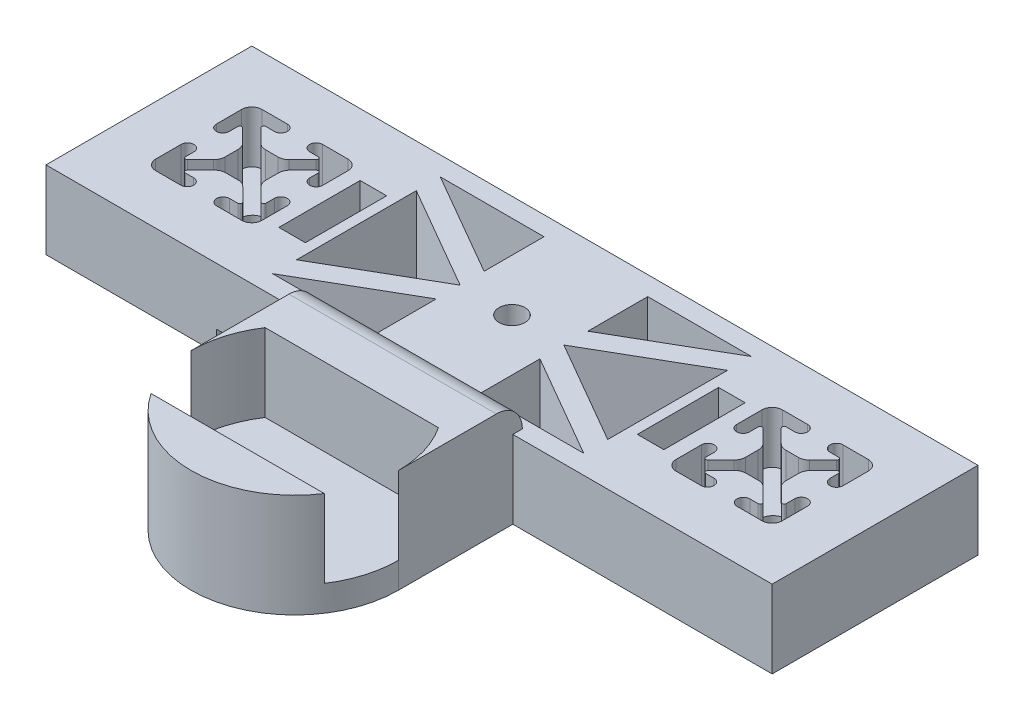
SolidWorks part; units mm, degrees
ref_plane "Front" through (0, 0, 0) normal (0, 0, 1) x (1, 0, 0)
ref_plane "Top" through (0, 0, 0) normal (0, 1, 0) x (1, 0, 0)
ref_plane "Right" through (0, 0, 0) normal (1, 0, 0) x (0, 0, -1)
sketch "Sketch1" plane through (0, 0, 0) normal (0, 1, 0) x (1, 0, 0)
  line L1 (0, 0) -> (177.8, 0)
  line L2 (0, 0) -> (0, 50.4)
  line L3 (0, 50.4) -> (177.8, 50.4)
  line L4 (177.8, 0) -> (177.8, 50.4)
  dimension "D1" = 177.8
  dimension "D2" = 50.4
extrude "Boss-Extrude1" add sketch "Sketch1" along normal blind 6.35
sketch "Sketch2" plane through (0, 6.35, 0) normal (0, 1, 0) x (1, 0, 0)
  line L0 (37.6996, 29.52) -> (37.6996, 35.7372) construction
  line L1 (35.7368, 37.7) -> (29.5196, 37.7) construction
  line L2 (29.5196, 35.56) -> (31.619, 35.56) construction
  line L3 (32.3326, 33.8353) -> (28.9966, 30.504) construction
  line L4 (26.7566, 29.5771) -> (23.643, 29.5771) construction
  line L5 (21.403, 30.504) -> (18.067, 33.8353) construction
  line L6 (18.7806, 35.56) -> (20.88, 35.56) construction
  line L7 (20.88, 37.7) -> (14.6628, 37.7) construction
  line L8 (12.7, 35.7372) -> (12.7, 29.52) construction
  line L9 (14.84, 29.52) -> (14.84, 31.5965) construction
  line L10 (16.5637, 32.3112) -> (19.7659, 29.1135) construction
  line L11 (20.743, 26.7568) -> (20.743, 23.6432) construction
  line L12 (19.7659, 21.2865) -> (16.5637, 18.0888) construction
  line L13 (14.84, 18.8035) -> (14.84, 20.88) construction
  line L14 (12.7, 20.88) -> (12.7, 14.6628) construction
  line L15 (14.6628, 12.7) -> (20.8121, 12.7) construction
  line L16 (20.8121, 14.84) -> (18.7806, 14.84) construction
  line L17 (18.067, 16.5647) -> (21.403, 19.896) construction
  line L18 (23.643, 20.8229) -> (26.7566, 20.8229) construction
  line L19 (28.9966, 19.896) -> (32.3326, 16.5647) construction
  line L20 (31.619, 14.84) -> (29.5875, 14.84) construction
  line L21 (29.5875, 12.7) -> (35.7368, 12.7) construction
  line L22 (37.6996, 14.6628) -> (37.6996, 20.88) construction
  line L23 (35.5596, 20.88) -> (35.5596, 18.8035) construction
  line L24 (33.8359, 18.0888) -> (30.6337, 21.2865) construction
  line L25 (29.6566, 23.6432) -> (29.6566, 26.7568) construction
  line L26 (30.6337, 29.1135) -> (33.8359, 32.3112) construction
  line L27 (35.5596, 31.5965) -> (35.5596, 29.52) construction
  line L28 (0, 50.4) -> (0, 0) construction
  line L29 (177.8, 50.4) -> (0, 50.4) construction
  line L30 (0, 0) -> (177.8, 0) construction
  line L31 (88.9, 50.4) -> (88.9, 0) construction
  line L32 (142.2404, 31.5965) -> (142.2404, 29.52) construction
  line L33 (147.1663, 29.1135) -> (143.9641, 32.3112) construction
  line L34 (148.1434, 23.6432) -> (148.1434, 26.7568) construction
  line L35 (143.9641, 18.0888) -> (147.1663, 21.2865) construction
  line L36 (142.2404, 20.88) -> (142.2404, 18.8035) construction
  line L37 (140.1004, 14.6628) -> (140.1004, 20.88) construction
  line L38 (148.2125, 12.7) -> (142.0632, 12.7) construction
  line L39 (146.181, 14.84) -> (148.2125, 14.84) construction
  line L40 (148.8034, 19.896) -> (145.4674, 16.5647) construction
  line L41 (154.157, 20.8229) -> (151.0434, 20.8229) construction
  line L42 (159.733, 16.5647) -> (156.397, 19.896) construction
  line L43 (156.9879, 14.84) -> (159.0194, 14.84) construction
  line L44 (163.1372, 12.7) -> (156.9879, 12.7) construction
  line L45 (165.1, 20.88) -> (165.1, 14.6628) construction
  line L46 (162.96, 18.8035) -> (162.96, 20.88) construction
  line L47 (158.0341, 21.2865) -> (161.2363, 18.0888) construction
  line L48 (157.057, 26.7568) -> (157.057, 23.6432) construction
  line L49 (161.2363, 32.3112) -> (158.0341, 29.1135) construction
  line L50 (162.96, 29.52) -> (162.96, 31.5965) construction
  line L51 (165.1, 35.7372) -> (165.1, 29.52) construction
  line L52 (156.92, 37.7) -> (163.1372, 37.7) construction
  line L53 (159.0194, 35.56) -> (156.92, 35.56) construction
  line L54 (156.397, 30.504) -> (159.733, 33.8353) construction
  line L55 (151.0434, 29.5771) -> (154.157, 29.5771) construction
  line L56 (145.4674, 33.8353) -> (148.8034, 30.504) construction
  line L57 (148.2804, 35.56) -> (146.181, 35.56) construction
  line L58 (142.0632, 37.7) -> (148.2804, 37.7) construction
  line L59 (140.1004, 29.52) -> (140.1004, 35.7372) construction
  line L60 (38.2076, 29.52) -> (38.2076, 35.7372)
  line L62 (0, 50.4) -> (0, 0)
  line L63 (0, 0) -> (177.8, 0)
  line L64 (177.8, 50.4) -> (177.8, 0)
  line L65 (35.7368, 38.208) -> (29.5196, 38.208)
  line L66 (29.5196, 35.052) -> (31.619, 35.052)
  line L67 (31.9737, 34.1948) -> (28.6376, 30.8635)
  line L68 (26.7566, 30.0851) -> (23.643, 30.0851)
  line L69 (21.762, 30.8635) -> (18.4259, 34.1948)
  line L70 (18.7806, 35.052) -> (20.88, 35.052)
  line L71 (20.88, 38.208) -> (14.6628, 38.208)
  line L72 (12.192, 35.7372) -> (12.192, 29.52)
  line L73 (15.348, 29.52) -> (15.348, 31.5965)
  line L74 (16.2047, 31.9517) -> (19.4069, 28.7541)
  line L75 (20.235, 26.7568) -> (20.235, 23.6432)
  line L76 (19.4069, 21.6459) -> (16.2047, 18.4483)
  line L77 (15.348, 18.8035) -> (15.348, 20.88)
  line L78 (12.192, 20.88) -> (12.192, 14.6628)
  line L79 (14.6628, 12.192) -> (20.8121, 12.192)
  line L80 (20.8121, 15.348) -> (18.7806, 15.348)
  line L81 (18.4259, 16.2052) -> (21.762, 19.5365)
  line L82 (23.643, 20.3149) -> (26.7566, 20.3149)
  line L83 (28.6376, 19.5365) -> (31.9737, 16.2052)
  line L84 (31.619, 15.348) -> (29.5875, 15.348)
  line L85 (29.5875, 12.192) -> (35.7368, 12.192)
  line L86 (38.2076, 14.6628) -> (38.2076, 20.88)
  line L87 (35.0516, 20.88) -> (35.0516, 18.8035)
  line L88 (34.1949, 18.4483) -> (30.9927, 21.6459)
  line L89 (30.1646, 23.6432) -> (30.1646, 26.7568)
  line L90 (30.9927, 28.7541) -> (34.1949, 31.9517)
  line L91 (35.0516, 31.5965) -> (35.0516, 29.52)
  line L92 (142.7484, 31.5965) -> (142.7484, 29.52)
  line L93 (139.5924, 29.52) -> (139.5924, 35.7372)
  line L94 (142.0632, 38.208) -> (148.2804, 38.208)
  line L95 (148.2804, 35.052) -> (146.181, 35.052)
  line L96 (145.8263, 34.1948) -> (149.1624, 30.8635)
  line L97 (151.0434, 30.0851) -> (154.157, 30.0851)
  line L98 (156.038, 30.8635) -> (159.3741, 34.1948)
  line L99 (159.0194, 35.052) -> (156.92, 35.052)
  line L100 (156.92, 38.208) -> (163.1372, 38.208)
  line L101 (165.608, 35.7372) -> (165.608, 29.52)
  line L102 (162.452, 29.52) -> (162.452, 31.5965)
  line L103 (161.5953, 31.9517) -> (158.3931, 28.7541)
  line L104 (157.565, 26.7568) -> (157.565, 23.6432)
  line L105 (158.3931, 21.6459) -> (161.5953, 18.4483)
  line L106 (162.452, 18.8035) -> (162.452, 20.88)
  line L107 (165.608, 20.88) -> (165.608, 14.6628)
  line L108 (163.1372, 12.192) -> (156.9879, 12.192)
  line L109 (156.9879, 15.348) -> (159.0194, 15.348)
  line L110 (159.3741, 16.2052) -> (156.038, 19.5365)
  line L111 (154.157, 20.3149) -> (151.0434, 20.3149)
  line L112 (149.1624, 19.5365) -> (145.8263, 16.2052)
  line L113 (146.181, 15.348) -> (148.2125, 15.348)
  line L114 (148.2125, 12.192) -> (142.0632, 12.192)
  line L115 (139.5924, 14.6628) -> (139.5924, 20.88)
  line L116 (142.7484, 20.88) -> (142.7484, 18.8035)
  line L117 (143.6051, 18.4483) -> (146.8073, 21.6459)
  line L118 (147.6354, 23.6432) -> (147.6354, 26.7568)
  line L119 (146.8073, 28.7541) -> (143.6051, 31.9517)
  line L120 (177.8, 50.4) -> (0, 50.4)
  arc A1 (37.6996, 35.7372) -> (35.7368, 37.7) centre (35.7368, 35.7372) ccw construction
  arc A2 (29.5196, 37.7) -> (29.5196, 35.56) centre (29.5196, 36.63) ccw construction
  arc A3 (31.619, 35.56) -> (32.3326, 33.8353) centre (31.619, 34.55) cw construction
  arc A4 (28.9966, 30.504) -> (26.7566, 29.5771) centre (26.7566, 32.7471) cw construction
  arc A5 (23.643, 29.5771) -> (21.403, 30.504) centre (23.643, 32.7471) cw construction
  arc A6 (18.067, 33.8353) -> (18.7806, 35.56) centre (18.7806, 34.55) cw construction
  arc A7 (20.88, 35.56) -> (20.88, 37.7) centre (20.88, 36.63) ccw construction
  arc A8 (14.6628, 37.7) -> (12.7, 35.7372) centre (14.6628, 35.7372) ccw construction
  arc A9 (12.7, 29.52) -> (14.84, 29.52) centre (13.77, 29.52) ccw construction
  arc A10 (14.84, 31.5965) -> (16.5637, 32.3112) centre (15.85, 31.5965) cw construction
  arc A11 (19.7659, 29.1135) -> (20.743, 26.7568) centre (17.4126, 26.7568) cw construction
  arc A12 (20.743, 23.6432) -> (19.7659, 21.2865) centre (17.4126, 23.6432) cw construction
  arc A13 (16.5637, 18.0888) -> (14.84, 18.8035) centre (15.85, 18.8035) cw construction
  arc A14 (14.84, 20.88) -> (12.7, 20.88) centre (13.77, 20.88) ccw construction
  arc A15 (12.7, 14.6628) -> (14.6628, 12.7) centre (14.6628, 14.6628) ccw construction
  arc A16 (20.8121, 12.7) -> (20.8121, 14.84) centre (20.8121, 13.77) ccw construction
  arc A17 (18.7806, 14.84) -> (18.067, 16.5647) centre (18.7806, 15.85) cw construction
  arc A18 (21.403, 19.896) -> (23.643, 20.8229) centre (23.643, 17.6529) cw construction
  arc A19 (26.7566, 20.8229) -> (28.9966, 19.896) centre (26.7566, 17.6529) cw construction
  arc A20 (32.3326, 16.5647) -> (31.619, 14.84) centre (31.619, 15.85) cw construction
  arc A21 (29.5875, 14.84) -> (29.5875, 12.7) centre (29.5875, 13.77) ccw construction
  arc A22 (35.7368, 12.7) -> (37.6996, 14.6628) centre (35.7368, 14.6628) ccw construction
  arc A23 (37.6996, 20.88) -> (35.5596, 20.88) centre (36.6296, 20.88) ccw construction
  arc A24 (35.5596, 18.8035) -> (33.8359, 18.0888) centre (34.5496, 18.8035) cw construction
  arc A25 (30.6337, 21.2865) -> (29.6566, 23.6432) centre (32.987, 23.6432) cw construction
  arc A26 (29.6566, 26.7568) -> (30.6337, 29.1135) centre (32.987, 26.7568) cw construction
  arc A27 (33.8359, 32.3112) -> (35.5596, 31.5965) centre (34.5496, 31.5965) cw construction
  arc A28 (35.5596, 29.52) -> (37.6996, 29.52) centre (36.6296, 29.52) ccw construction
  arc A29 (142.2404, 29.52) -> (140.1004, 29.52) centre (141.1704, 29.52) cw construction
  arc A30 (143.9641, 32.3112) -> (142.2404, 31.5965) centre (143.2504, 31.5965) ccw construction
  arc A31 (148.1434, 26.7568) -> (147.1663, 29.1135) centre (144.813, 26.7568) ccw construction
  arc A32 (147.1663, 21.2865) -> (148.1434, 23.6432) centre (144.813, 23.6432) ccw construction
  arc A33 (142.2404, 18.8035) -> (143.9641, 18.0888) centre (143.2504, 18.8035) ccw construction
  arc A34 (140.1004, 20.88) -> (142.2404, 20.88) centre (141.1704, 20.88) cw construction
  arc A35 (142.0632, 12.7) -> (140.1004, 14.6628) centre (142.0632, 14.6628) cw construction
  arc A36 (148.2125, 14.84) -> (148.2125, 12.7) centre (148.2125, 13.77) cw construction
  arc A37 (145.4674, 16.5647) -> (146.181, 14.84) centre (146.181, 15.85) ccw construction
  arc A38 (151.0434, 20.8229) -> (148.8034, 19.896) centre (151.0434, 17.6529) ccw construction
  arc A39 (156.397, 19.896) -> (154.157, 20.8229) centre (154.157, 17.6529) ccw construction
  arc A40 (159.0194, 14.84) -> (159.733, 16.5647) centre (159.0194, 15.85) ccw construction
  arc A41 (156.9879, 12.7) -> (156.9879, 14.84) centre (156.9879, 13.77) cw construction
  arc A42 (165.1, 14.6628) -> (163.1372, 12.7) centre (163.1372, 14.6628) cw construction
  arc A43 (162.96, 20.88) -> (165.1, 20.88) centre (164.03, 20.88) cw construction
  arc A44 (161.2363, 18.0888) -> (162.96, 18.8035) centre (161.95, 18.8035) ccw construction
  arc A45 (157.057, 23.6432) -> (158.0341, 21.2865) centre (160.3874, 23.6432) ccw construction
  arc A46 (158.0341, 29.1135) -> (157.057, 26.7568) centre (160.3874, 26.7568) ccw construction
  arc A47 (162.96, 31.5965) -> (161.2363, 32.3112) centre (161.95, 31.5965) ccw construction
  arc A48 (165.1, 29.52) -> (162.96, 29.52) centre (164.03, 29.52) cw construction
  arc A49 (163.1372, 37.7) -> (165.1, 35.7372) centre (163.1372, 35.7372) cw construction
  arc A50 (156.92, 35.56) -> (156.92, 37.7) centre (156.92, 36.63) cw construction
  arc A51 (159.733, 33.8353) -> (159.0194, 35.56) centre (159.0194, 34.55) ccw construction
  arc A52 (154.157, 29.5771) -> (156.397, 30.504) centre (154.157, 32.7471) ccw construction
  arc A53 (148.8034, 30.504) -> (151.0434, 29.5771) centre (151.0434, 32.7471) ccw construction
  arc A54 (146.181, 35.56) -> (145.4674, 33.8353) centre (146.181, 34.55) ccw construction
  arc A55 (148.2804, 37.7) -> (148.2804, 35.56) centre (148.2804, 36.63) cw construction
  arc A56 (140.1004, 35.7372) -> (142.0632, 37.7) centre (142.0632, 35.7372) cw construction
  arc A58 (38.2076, 35.7372) -> (35.7368, 38.208) centre (35.7368, 35.7372) ccw
  arc A59 (29.5196, 38.208) -> (29.5196, 35.052) centre (29.5196, 36.63) ccw
  arc A60 (31.619, 35.052) -> (31.9737, 34.1948) centre (31.619, 34.55) cw
  arc A61 (28.6376, 30.8635) -> (26.7566, 30.0851) centre (26.7566, 32.7471) cw
  arc A62 (23.643, 30.0851) -> (21.762, 30.8635) centre (23.643, 32.7471) cw
  arc A63 (18.4259, 34.1948) -> (18.7806, 35.052) centre (18.7806, 34.55) cw
  arc A64 (20.88, 35.052) -> (20.88, 38.208) centre (20.88, 36.63) ccw
  arc A65 (14.6628, 38.208) -> (12.192, 35.7372) centre (14.6628, 35.7372) ccw
  arc A66 (12.192, 29.52) -> (15.348, 29.52) centre (13.77, 29.52) ccw
  arc A67 (15.348, 31.5965) -> (16.2047, 31.9517) centre (15.85, 31.5965) cw
  arc A68 (19.4069, 28.7541) -> (20.235, 26.7568) centre (17.4126, 26.7568) cw
  arc A69 (20.235, 23.6432) -> (19.4069, 21.6459) centre (17.4126, 23.6432) cw
  arc A70 (16.2047, 18.4483) -> (15.348, 18.8035) centre (15.85, 18.8035) cw
  arc A71 (15.348, 20.88) -> (12.192, 20.88) centre (13.77, 20.88) ccw
  arc A72 (12.192, 14.6628) -> (14.6628, 12.192) centre (14.6628, 14.6628) ccw
  arc A73 (20.8121, 12.192) -> (20.8121, 15.348) centre (20.8121, 13.77) ccw
  arc A74 (18.7806, 15.348) -> (18.4259, 16.2052) centre (18.7806, 15.85) cw
  arc A75 (21.762, 19.5365) -> (23.643, 20.3149) centre (23.643, 17.6529) cw
  arc A76 (26.7566, 20.3149) -> (28.6376, 19.5365) centre (26.7566, 17.6529) cw
  arc A77 (31.9737, 16.2052) -> (31.619, 15.348) centre (31.619, 15.85) cw
  arc A78 (29.5875, 15.348) -> (29.5875, 12.192) centre (29.5875, 13.77) ccw
  arc A79 (35.7368, 12.192) -> (38.2076, 14.6628) centre (35.7368, 14.6628) ccw
  arc A80 (38.2076, 20.88) -> (35.0516, 20.88) centre (36.6296, 20.88) ccw
  arc A81 (35.0516, 18.8035) -> (34.1949, 18.4483) centre (34.5496, 18.8035) cw
  arc A82 (30.9927, 21.6459) -> (30.1646, 23.6432) centre (32.987, 23.6432) cw
  arc A83 (30.1646, 26.7568) -> (30.9927, 28.7541) centre (32.987, 26.7568) cw
  arc A84 (34.1949, 31.9517) -> (35.0516, 31.5965) centre (34.5496, 31.5965) cw
  arc A85 (35.0516, 29.52) -> (38.2076, 29.52) centre (36.6296, 29.52) ccw
  arc A86 (142.7484, 29.52) -> (139.5924, 29.52) centre (141.1704, 29.52) cw
  arc A87 (139.5924, 35.7372) -> (142.0632, 38.208) centre (142.0632, 35.7372) cw
  arc A88 (148.2804, 38.208) -> (148.2804, 35.052) centre (148.2804, 36.63) cw
  arc A89 (146.181, 35.052) -> (145.8263, 34.1948) centre (146.181, 34.55) ccw
  arc A90 (149.1624, 30.8635) -> (151.0434, 30.0851) centre (151.0434, 32.7471) ccw
  arc A91 (154.157, 30.0851) -> (156.038, 30.8635) centre (154.157, 32.7471) ccw
  arc A92 (159.3741, 34.1948) -> (159.0194, 35.052) centre (159.0194, 34.55) ccw
  arc A93 (156.92, 35.052) -> (156.92, 38.208) centre (156.92, 36.63) cw
  arc A94 (163.1372, 38.208) -> (165.608, 35.7372) centre (163.1372, 35.7372) cw
  arc A95 (165.608, 29.52) -> (162.452, 29.52) centre (164.03, 29.52) cw
  arc A96 (162.452, 31.5965) -> (161.5953, 31.9517) centre (161.95, 31.5965) ccw
  arc A97 (158.3931, 28.7541) -> (157.565, 26.7568) centre (160.3874, 26.7568) ccw
  arc A98 (157.565, 23.6432) -> (158.3931, 21.6459) centre (160.3874, 23.6432) ccw
  arc A99 (161.5953, 18.4483) -> (162.452, 18.8035) centre (161.95, 18.8035) ccw
  arc A100 (162.452, 20.88) -> (165.608, 20.88) centre (164.03, 20.88) cw
  arc A101 (165.608, 14.6628) -> (163.1372, 12.192) centre (163.1372, 14.6628) cw
  arc A102 (156.9879, 12.192) -> (156.9879, 15.348) centre (156.9879, 13.77) cw
  arc A103 (159.0194, 15.348) -> (159.3741, 16.2052) centre (159.0194, 15.85) ccw
  arc A104 (156.038, 19.5365) -> (154.157, 20.3149) centre (154.157, 17.6529) ccw
  arc A105 (151.0434, 20.3149) -> (149.1624, 19.5365) centre (151.0434, 17.6529) ccw
  arc A106 (145.8263, 16.2052) -> (146.181, 15.348) centre (146.181, 15.85) ccw
  arc A107 (148.2125, 15.348) -> (148.2125, 12.192) centre (148.2125, 13.77) cw
  arc A108 (142.0632, 12.192) -> (139.5924, 14.6628) centre (142.0632, 14.6628) cw
  arc A109 (139.5924, 20.88) -> (142.7484, 20.88) centre (141.1704, 20.88) cw
  arc A110 (142.7484, 18.8035) -> (143.6051, 18.4483) centre (143.2504, 18.8035) ccw
  arc A111 (146.8073, 21.6459) -> (147.6354, 23.6432) centre (144.813, 23.6432) ccw
  arc A112 (147.6354, 26.7568) -> (146.8073, 28.7541) centre (144.813, 26.7568) ccw
  arc A113 (143.6051, 31.9517) -> (142.7484, 31.5965) centre (143.2504, 31.5965) ccw
  dimension "D2" = 1.07
  dimension "D3" = 3.17
  dimension "D4" = 3.3305
  dimension "D8" = 1.9628
  dimension "D9" = 1.01
  dimension "D5" = 12.7
  dimension "D6" = 12.7
  dimension "D7" = 12.7
  dimension "D10" = 16.5637
  dimension "D12" = 0.508
  dimension "D13" = 0.508
extrude "Boss-Extrude2" add sketch "Sketch2" along normal blind 12.7
sketch "Sketch3" plane through (0, 19.05, 0) normal (0, 1, 0) x (1, 0, 0)
  line L0 (177.8, 50.4) -> (0, 50.4) construction
  line L1 (0, 50.4) -> (0, 0) construction
  circle A0 centre (88.9, 25.2) radius 3.175
  point P4 (88.9, 50.4)
  point P7 (0, 25.2)
  dimension "D1" = 6.35
extrude "Cut-Extrude1" cut sketch "Sketch3" against normal blind 10.16
sketch "Sketch4" plane through (0, 19.05, 0) normal (0, 1, 0) x (1, 0, 0)
  line L0 (50.8, 45.7306) -> (76.2, 45.7306)
  line L1 (76.2, 45.7306) -> (76.2, 31.0659)
  line L2 (76.2, 31.0659) -> (50.8, 45.7306)
  line L3 (76.2, 19.3341) -> (76.2, 4.6694)
  line L4 (76.2, 4.6694) -> (50.8, 4.6694)
  line L5 (50.8, 4.6694) -> (76.2, 19.3341)
  line L6 (50.8, 39.8647) -> (50.8, 10.5353)
  line L7 (50.8, 10.5353) -> (76.2, 25.2)
  line L8 (76.2, 25.2) -> (50.8, 39.8647)
  line L9 (0, 50.4) -> (0, 0) construction
  line L10 (88.9, 50.4) -> (88.9, 0) construction
  line L11 (177.8, 50.4) -> (0, 50.4) construction
  line L12 (0, 0) -> (177.8, 0) construction
  line L13 (101.6, 25.2) -> (127, 39.8647)
  line L14 (127, 10.5353) -> (101.6, 25.2)
  line L15 (127, 39.8647) -> (127, 10.5353)
  line L16 (127, 4.6694) -> (101.6, 19.3341)
  line L17 (101.6, 4.6694) -> (127, 4.6694)
  line L18 (101.6, 19.3341) -> (101.6, 4.6694)
  line L19 (101.6, 31.0659) -> (127, 45.7306)
  line L20 (101.6, 45.7306) -> (101.6, 31.0659)
  line L21 (127, 45.7306) -> (101.6, 45.7306)
  point P18 (88.9, 25.2)
  dimension "D1" = 25.4
  dimension "D2" = 25.4
  dimension "D3" = 50.8
  dimension "D4" = 5.08
  dimension "D5" = 5.08
  dimension "D7" = 60
extrude "Cut-Extrude2" cut sketch "Sketch4" against normal through all
sketch "Sketch5" plane through (0, 19.05, 0) normal (0, 1, 0) x (1, 0, 0)
  line L0 (0, 50.4) -> (0, 0) construction
  line L1 (41.7636, 35.15) -> (48.2636, 35.15)
  line L2 (41.7636, 35.15) -> (41.7636, 15.25)
  line L3 (41.7636, 15.25) -> (48.2636, 15.25)
  line L4 (48.2636, 35.15) -> (48.2636, 15.25)
  line L5 (38.2076, 29.52) -> (38.2076, 35.7372) construction
  point P6 (0, 25.2)
  point P7 (48.2636, 25.2)
  dimension "D1" = 6.5
  dimension "D2" = 19.9
  dimension "D3" = 3.556
extrude "Cut-Extrude3" cut sketch "Sketch5" against normal blind 10.2
sketch "Sketch6" plane through (0, 8.85, 0) normal (0, 1, 0) x (1, 0, 0)
  line L0 (48.2636, 15.25) -> (48.2636, 35.15) construction
  line L1 (41.7636, 35.15) -> (48.2636, 35.15)
  line L2 (41.7636, 35.15) -> (41.7636, 30.578)
  line L3 (41.7636, 30.578) -> (48.2636, 30.578)
  line L4 (48.2636, 35.15) -> (48.2636, 30.578)
  line L5 (41.7636, 35.15) -> (41.7636, 15.25) construction
  line L6 (48.2636, 15.25) -> (48.2636, 35.15) construction
  line L7 (41.7636, 27.486) -> (48.2636, 27.486)
  line L8 (41.7636, 27.486) -> (41.7636, 22.914)
  line L9 (41.7636, 22.914) -> (48.2636, 22.914)
  line L10 (48.2636, 27.486) -> (48.2636, 22.914)
  line L12 (41.7636, 15.25) -> (48.2636, 15.25)
  line L13 (41.7636, 15.25) -> (41.7636, 19.822)
  line L14 (41.7636, 19.822) -> (48.2636, 19.822)
  line L15 (48.2636, 15.25) -> (48.2636, 19.822)
  line L16 (41.7636, 25.2) -> (0, 25.2) construction
  line L17 (0, 50.4) -> (0, 0) construction
  dimension "D1" = 4.572
extrude "Cut-Extrude4" cut sketch "Sketch6" against normal through all
ref_plane "Plane1" through (88.9, 0, 0) normal (-1, 0, 0) x (0, 0, 1)
mirror "Mirror1" about plane through (88.9, 0, 0) normal (-1, 0, 0) of "Cut-Extrude4", "Cut-Extrude3"
sketch "Sketch7" plane through (0, 6.35, 0) normal (0, 1, 0) x (1, 0, 0)
  line L0 (26.7566, 30.0851) -> (23.643, 30.0851) construction
  line L1 (30.1646, 23.6432) -> (30.1646, 26.7568) construction
  circle A0 centre (25.3386, 25.2591) radius 2.921
  dimension "D1" = 5.842
  dimension "D2" = 4.826
  dimension "D3" = 4.826
extrude "Cut-Extrude5" cut sketch "Sketch7" against normal through all both and the other way through all
sketch "Sketch8" plane through (0, 6.35, 0) normal (0, 1, 0) x (1, 0, 0)
  line L0 (154.157, 30.0851) -> (151.0434, 30.0851) construction
  line L1 (157.565, 23.6432) -> (157.565, 26.7568) construction
  circle A0 centre (152.739, 25.2591) radius 2.921
  dimension "D1" = 5.842
  dimension "D2" = 4.826
  dimension "D3" = 4.826
extrude "Cut-Extrude6" cut sketch "Sketch8" against normal through all both and the other way through all
chamfer "Chamfer2" distance 3.302 angle 45 1 edges at (152.739, 0, -22.3381)
chamfer "Chamfer3" distance 3.302 angle 45 1 edges at (25.3386, 0, -22.3381)
sketch "Sketch9" plane through (0, 0, 0) normal (0, 1, 0) x (1, 0, 0)
  line L0 (88.9, 22.025) -> (88.9, -28) construction
  line L1 (85.725, 25.2) -> (92.075, 25.2) construction
  line L2 (63.5, -28) -> (63.5, 0)
  line L3 (0, 0) -> (177.8, 0) construction
  line L4 (114.3, -28) -> (114.3, 0)
  line L6 (112.4272, 4.6694) -> (112.4272, 0) construction
  line L7 (101.6, 4.6694) -> (127, 4.6694) construction
  line L10 (114.3, 0) -> (114.3, 2.3347)
  line L11 (114.3, 2.3347) -> (63.5, 2.3347)
  line L12 (63.5, 0) -> (63.5, 2.3347)
  circle A0 centre (88.9, 25.2) radius 3.175 construction
  circle A1 centre (88.9, 25.2) radius 3.175 construction
  arc A2 (63.5, -28) -> (114.3, -28) centre (88.9, -28) ccw
  point P10 (88.9, 25.2)
  point P20 (112.4272, 2.3347)
  dimension "D1" = 50.8
  dimension "D2" = 53.2
sketch "Sketch11" plane through (0, 0, 0) normal (0, 1, 0) x (1, 0, 0)
  line L0 (0, 0) -> (177.8, 0) construction
  line L2 (41.7636, 15.25) -> (41.7636, 0)
  line L3 (41.7636, 0) -> (48.2636, 0)
  line L4 (48.2636, 15.25) -> (48.2636, 0)
  line L5 (48.2636, 15.25) -> (48.2636, 35.15) construction
  line L6 (177.8, 50.4) -> (0, 50.4) construction
  line L8 (41.7636, 35.15) -> (41.7636, 50.4)
  line L9 (41.7636, 50.4) -> (48.2636, 50.4)
  line L10 (48.2636, 35.15) -> (48.2636, 50.4)
  line L11 (41.7636, 35.15) -> (41.7636, 15.25)
  line L12 (48.2636, 35.15) -> (48.2636, 15.25)
extrude "Cut-Extrude8" cut sketch "Sketch11" along normal blind 5.08
extrude "Boss-Extrude4" add sketch "Sketch9" along normal blind 25.4
sketch "Sketch13" plane through (0, 25.4, 0) normal (0, 1, 0) x (1, 0, 0)
  line L0 (88.9, 22.025) -> (88.9, -33.4485) construction
  line L1 (88.9, 28.375) -> (88.9, 22.025) construction
  line L2 (67.6868, -14.03) -> (110.1132, -14.03)
  line L3 (67.6868, -41.97) -> (110.1132, -41.97)
  line L4 (88.9, -14.03) -> (88.9, -41.97) construction
  arc A0 (67.6868, -14.03) -> (67.6868, -41.97) centre (88.9, -28) ccw
  circle A1 centre (88.9, 25.2) radius 3.175 construction
  arc A2 (63.5, -28) -> (114.3, -28) centre (88.9, -28) ccw construction
  circle A3 centre (88.9, 25.2) radius 3.175 construction
  arc A4 (110.1132, -41.97) -> (110.1132, -14.03) centre (88.9, -28) ccw
  point P7 (88.9, -53.4)
  point P20 (0, 0)
  point P21 (88.9, -28)
  dimension "D1" = 50.8
  dimension "D2" = 27.94
extrude "Cut-Extrude9" cut sketch "Sketch13" against normal blind 19.05
fillet "Fillet2" radius 6.35 1 edges at (88.9, 25.4, -2.3347)
